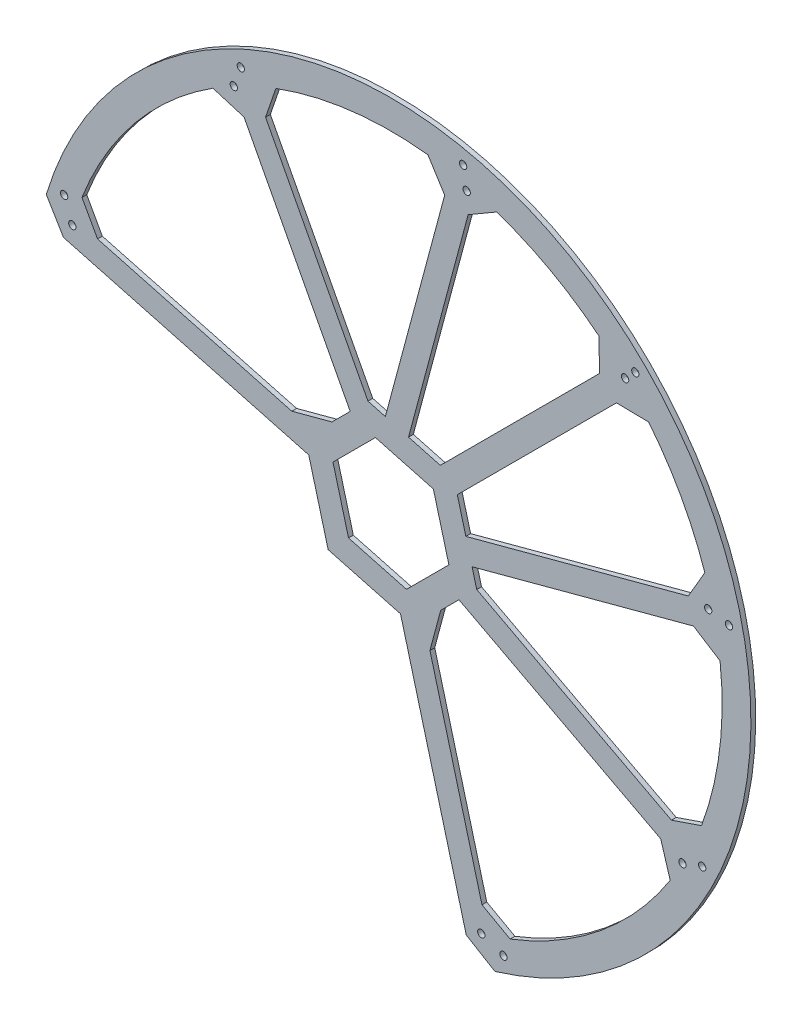
SolidWorks part; units mm, degrees
material "Thornel Mat VMA"
ref_plane "前视基准面" through (0, 0, 0) normal (0, 0, 1) x (1, 0, 0)
ref_plane "上视基准面" through (0, 0, 0) normal (0, 1, 0) x (1, 0, 0)
ref_plane "右视基准面" through (0, 0, 0) normal (1, 0, 0) x (0, 0, -1)
sketch "草图2" plane through (0, 0, 0) normal (0, 0, 1) x (1, 0, 0)
  line L0 (-36.3678, -286.976) -> (20.3558, -230.2524)
  line L1 (112.9865, -137.6211) -> (139.1494, -111.4581) construction
  line L3 (112.9868, -137.6214) -> (-24.2505, -152.111) construction
  line L20 (112.9865, -137.6211) -> (103.4102, -101.8818) construction
  line L59 (112.9865, -137.6211) -> (-37.0124, -138.1873) construction
  line L61 (148.7258, -147.1974) -> (249.3455, -200.1224)
  line L62 (112.9865, -137.6211) -> (77.2472, -128.0448) construction
  line L63 (141.3231, -154.6001) -> (244.8781, -209.069)
  line L68 (120.316, -106.4121) -> (150.8448, 7.5228)
  line L80 (95.3088, -155.2987) -> (119.457, -161.7692)
  line L81 (110.6567, -103.8239) -> (141.0819, 9.7243)
  line L82 (119.457, -161.7692) -> (137.1346, -144.0915)
  line L83 (137.1346, -144.0915) -> (130.6642, -119.9434)
  line L84 (130.6642, -119.9434) -> (106.516, -113.4729)
  line L85 (106.516, -113.4729) -> (88.8384, -131.1506)
  line L86 (88.8384, -131.1506) -> (95.3088, -155.2987)
  line L87 (86.8235, -163.784) -> (122.5628, -173.3603)
  line L88 (122.5628, -173.3603) -> (148.7258, -147.1974)
  line L89 (148.7258, -147.1974) -> (139.1494, -111.4581)
  line L90 (139.1494, -111.4581) -> (103.4102, -101.8818)
  line L91 (103.4102, -101.8818) -> (77.2472, -128.0448)
  line L92 (77.2472, -128.0448) -> (86.8235, -163.784)
  line L93 (139.1494, -111.4581) -> (140.633, -109.9481) construction
  line L97 (146.7842, -139.9514) -> (260.3324, -109.5263)
  line L99 (144.196, -130.2922) -> (258.131, -99.7634)
  line L100 (112.9868, -137.6214) -> (122.5628, -173.3603) construction
  line L104 (122.5628, -173.3603) -> (151.809, -282.5107) construction
  line L105 (126.6453, -169.2778) -> (156.6171, -281.1361)
  line L107 (116.9862, -171.8665) -> (126.6453, -169.2778)
  line L108 (116.9862, -171.8665) -> (143.8501, -272.126)
  line L111 (103.4108, -101.8824) -> (50.4858, -1.2627)
  line L112 (143.8501, -272.126) -> (146.9578, -283.7242)
  line L113 (96.0081, -109.2851) -> (41.5392, -5.7301)
  line L114 (77.2478, -128.0453) -> (-31.9025, -98.7991) construction
  line L116 (78.7417, -133.622) -> (-21.5178, -106.758)
  line L118 (133.5731, -109.9639) -> (215.4585, -28.0786)
  line L119 (81.3303, -123.9629) -> (-30.5279, -93.991)
  line L120 (-21.5178, -106.758) -> (-33.1161, -103.6503)
  line L121 (57.4813, -193.1268) -> (66.3368, -184.2713) construction
  line L122 (140.6439, -117.0354) -> (222.5295, -35.1497)
  line L129 (20.3558, -230.2524) -> (112.9868, -137.6214)
  line L130 (-3.2118, -253.82) -> (8.8363, -241.7719) construction
  circle A5 centre (112.9865, -137.6211) radius 21.6506 construction
  circle A9 centre (112.9865, -137.6211) radius 32.0429 construction
  circle A25 centre (112.9865, -137.6211) radius 137.9998
  circle A26 centre (112.9868, -137.6214) radius 150.0003
  point P3 (110.3981, -127.9609)
  point P46 (219.6545, -32.1602)
  point P48 (222.3705, -34.9799)
  dimension "D3" = 10
  dimension "D6" = 5
  dimension "D7" = 25
  dimension "D8" = 10
  dimension "D1" = 131
  dimension "D5" = 180
  dimension "D9" = 138
  dimension "D10" = 150
  dimension "D2" = 37
  dimension "D4" = 10
  dimension "D11" = 5
  dimension "D12" = 90
  dimension "D13" = 180
  dimension "D15" = 5
extrude "凸台-拉伸11" add sketch "草图2" against normal blind 2
chamfer "倒角1" distance 10 14 edges at (146.9578, -283.7242, -1) (147.7388, -4.0688, -1) (137.9669, -1.9011, -1) (-18.9297, -97.0987, -1) (-33.1161, -103.6503, -1) (56.0811, -11.9003, -1) (47.1259, -16.3514, -1) (153.5092, -269.5371, -1) (234.256, -203.4819, -1) (238.7072, -194.5267, -1) (248.7066, -112.6414, -1) (246.539, -102.8694, -1) (206.9678, -36.5693, -1) (214.0388, -43.6404, -1)
chamfer "倒角3" distance 10 2 edges at (81.3294, -123.9626, -1) (126.6453, -169.2778, -1)
sketch "草图4" plane through (0, 0, -2) normal (0, 0, -1) x (-1, 0, 0)
  line L0 (-245.4428, -207.658) -> (-259.748, -168.623)
  line L1 (-232.6013, -211.9796) -> (-245.4428, -207.658) construction
  line L2 (-259.748, -168.623) -> (-245.4428, -207.658) construction
  line L3 (-262.8035, -130.2132) -> (-259.748, -168.623) construction
  line L4 (-259.748, -168.623) -> (-262.8035, -130.2132)
  line L5 (-262.8035, -130.2132) -> (-258.2914, -100.386)
  line L6 (-245.1607, -66.6991) -> (-258.2914, -100.386) construction
  line L7 (-258.2914, -100.386) -> (-245.1607, -66.6991)
  line L8 (-219.0526, -31.5556) -> (-245.1607, -66.6991) construction
  line L9 (-245.1607, -66.6991) -> (-219.0526, -31.5556)
  line L10 (-245.4428, -207.658) -> (-222.3564, -240.2775)
  line L11 (-222.3564, -240.2775) -> (-192.5939, -264.7541)
  line L12 (-192.5939, -264.7541) -> (-167.8274, -277.2371)
  line L13 (-112.9865, -137.6216) -> (-94.6898, -286.5015)
  line L15 (-112.9865, -137.6216) -> (-161.7963, -279.4582) construction
  line L16 (-112.9865, -137.6216) -> (-153.9169, -281.9293) construction
  line L17 (-8.8363, -241.7719) -> (3.2118, -253.82) construction
  circle A0 centre (-253.8094, -107.5398) radius 1.52
  circle A1 centre (-245.1865, -106.0608) radius 1.52
  circle A2 centre (-112.9865, -137.6216) radius 150
  circle A3 centre (-112.9865, -137.6216) radius 3.6
  circle A4 centre (-20.3558, -230.2524) radius 1.52
  circle A5 centre (-242.6883, -200.1793) radius 1.52
  circle A6 centre (-234.4637, -203.0991) radius 1.52
  circle A7 centre (-214.8099, -35.7982) radius 1.52
  circle A8 centre (-210.5673, -40.0409) radius 1.52
  circle A9 centre (-159.8439, -273.7847) radius 1.52
  circle A10 centre (-150.6425, -270.3847) radius 1.52
  circle A11 centre (-143.0684, 3.2013) radius 1.52
  circle A12 centre (-144.5473, -5.4216) radius 1.52
  circle A13 centre (-50.4289, -7.9199) radius 1.52
  circle A14 centre (-47.509, -16.1445) radius 1.52
  circle A15 centre (23.1766, -90.7643) radius 1.52
  circle A16 centre (19.7765, -99.9657) radius 1.52
  dimension "D1" = 150
  dimension "D2" = 6
  dimension "D3" = 12
extrude "切除-拉伸1" cut sketch "草图4" against normal blind 10 contours A1 | A0 | A6 | A5 | A10 | A9 | A8 | A7 | A12 | A11 | A14 | A13 | A16 | A15
